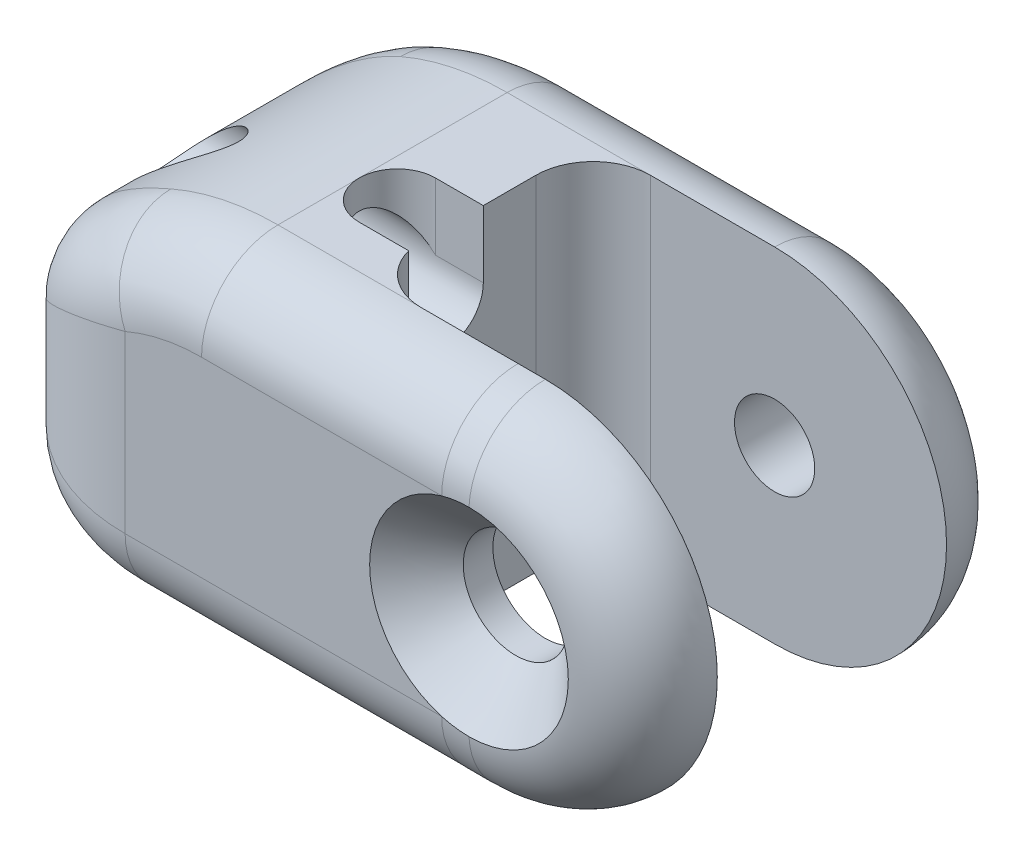
SolidWorks part; units mm, degrees
ref_plane "Front Plane" through (0, 0, 0) normal (0, 0, 1) x (1, 0, 0)
ref_plane "Top Plane" through (0, 0, 0) normal (0, 1, 0) x (1, 0, 0)
ref_plane "Right Plane" through (0, 0, 0) normal (1, 0, 0) x (0, 0, -1)
sketch "Sketch2" plane through (0, 0, 0) normal (0, 1, 0) x (1, 0, 0)
  line L0 (-3.5, 10) -> (23.5, 10)
  line L1 (23.5, 10) -> (23.5, 6)
  line L2 (23.5, 6) -> (8, 6)
  line L3 (5, 3) -> (5, -3)
  line L4 (8, -6) -> (23.5, -6)
  line L5 (23.5, -6) -> (23.5, -10)
  line L8 (-49.3622, 0) -> (56.3776, 0) construction
  line L9 (0, 21.2372) -> (0, -19.0689) construction
  line L10 (5, 3) -> (8, 3) construction
  line L11 (8, 3) -> (8, 6) construction
  line L16 (-3.5, -10) -> (23.5, -10)
  arc A0 (8, 6) -> (5, 3) centre (8, 3) ccw
  arc A1 (8, -6) -> (5, -3) centre (8, -3) cw
  arc A3 (-3.5, 10) -> (-3.5, -10) centre (-3.5, 0) ccw
  point P13 (8, 3)
  dimension "D2" = 20
  dimension "D3" = 4
  dimension "D4" = 18.5
  dimension "D5" = 12
  dimension "D6" = 3
  dimension "D7" = 3
  dimension "D8" = 5
  dimension "D9" = 27
extrude "Boss-Extrude1" add sketch "Sketch2" along normal blind 18
sketch "Sketch5" plane through (0, 0, 10) normal (0, 0, 1) x (1, 0, 0)
  line L0 (-13.5058, 9) -> (31.8434, 9) construction
  line L1 (-3.5, 18) -> (-3.5, 0) construction
  line L2 (23.5, 18) -> (23.5, 0) construction
  line L3 (-3.5, 18) -> (23.5, 18) construction
  line L4 (14.5, 18) -> (14.5, 0) construction
  line L5 (-13.5, 0) -> (-3.5, 0) construction
  line L7 (-13.5, 0) -> (-13.5, 4)
  line L8 (-13.5, 0) -> (14.5, 0)
  line L9 (0.5, 18) -> (14.5, 18)
  arc A1 (14.5, 0) -> (14.5, 18) centre (14.5, 9) ccw
  arc A2 (0.5, 18) -> (-13.5, 4) centre (0.5, 4) ccw
  dimension "D2" = 4
  dimension "D1" = 9
  dimension "D3" = 10
extrude "Cut-Extrude1" cut sketch "Sketch5" against normal blind 20 flip side to cut
sketch "Sketch6" plane through (0, 0, 10) normal (0, 0, 1) x (1, 0, 0)
  line L0 (14.5, 0) -> (14.5, 18) construction
  point P4 (14.5, 9)
hole_wizard "CSK for M5 Countersunk Flat Head Screw1" positions "Sketch7" profile "Sketch8" countersink size "M5" standard "DIN" end condition up to next
sketch "Sketch7" plane through (0, 0, 10) normal (0, 0, 1) x (1, 0, 0)
  point P0 (14.5, 9)
sketch "Sketch8" plane through (14.5, 9, 10) normal (1, 0, 0) x (0, -1, 0)
  line L0 (0, 0) -> (0, 4)
  line L1 (0, 4) -> (2.75, 4)
  line L2 (2.75, 4) -> (2.75, 2.45)
  line L3 (2.75, 2.45) -> (5.2, 0)
  line L5 (5.2, 0) -> (0, 0)
  line L6 (-2.75, 2.45) -> (-5.2, 0) construction
  line L11 (0, -6.35) -> (0, 107.95) construction
  dimension "Thru Hole Dia." = 5.5
  dimension "Thru Hole Depth" = 4
  dimension "Near C'Sink Dia." = 10.4
  dimension "Near C'Sink Angle" = 90
hole_wizard "M5 Tapped Hole1" positions "Sketch9" profile "Sketch11" tap size "M5" standard "DIN" end condition through all
sketch "Sketch9" plane through (0, 0, 10) normal (0, 0, 1) x (1, 0, 0)
  point P0 (14.5, 9)
sketch "Sketch11" plane through (14.5, 9, 10) normal (1, 0, 0) x (0, -1, 0)
  line L0 (0, 0) -> (0, 20)
  line L1 (0, 20) -> (2.1, 20)
  line L2 (2.1, 20) -> (2.1, 3.1)
  line L3 (2.1, 3.1) -> (5.2, 0)
  line L5 (5.2, 0) -> (0, 0)
  line L6 (-2.1, 3.1) -> (-5.2, 0) construction
  line L11 (0, -6.35) -> (0, 107.95) construction
  dimension "Thru Tap Drill Dia." = 4.2
  dimension "Thru Tap Drill Depth" = 20
  dimension "Near C'Sink Dia." = 10.4
  dimension "Near C'Sink Angle" = 90
cosmetic thread "Hole Thread1" parameters "D2"=5
fillet "Fillet2" radius 4 11 edges at (-9.0658, 14.2223, -8.308) (-1.5212, 17.8533, -10) (7.5, 18, -10) (23.5, 9, -10) (-9.0658, 14.2223, 8.308) (-1.5212, 17.8533, 10) (7.5, 18, 10) (23.5, 9, 10) (5.5, 0, 10) (-13.5, 0, 0) (5.5, 0, -10)
sketch "Sketch13" plane through (5, 0, 0) normal (1, 0, 0) x (0, 0, -1)
  line L0 (-1.75, -2.2721) -> (-1.75, 20.0856) construction
  line L1 (-3, 0) -> (3, 0) construction
  line L2 (-3, 18) -> (3, 18) construction
  circle A0 centre (-1.75, 14.5) radius 2
  point P4 (0, 0)
  dimension "D2" = 3.5
  dimension "D3" = 4
  dimension "D1" = 1.75
extrude "Cut-Extrude2" cut sketch "Sketch13" against normal through all both and the other way through all
sketch "Sketch14" plane through (0, 18, 0) normal (0, 1, 0) x (1, 0, 0)
  line L0 (5, 0) -> (-14.1432, 0) construction
  line L3 (5, -3) -> (5, 3) construction
  line L4 (2.5, -3.75) -> (7.4532, -3.75)
  line L5 (2.5, 0.25) -> (7.4532, 0.25)
  line L6 (7.4532, 0.25) -> (7.4532, -3.75)
  arc A0 (2.5, 0.25) -> (2.5, -3.75) centre (2.5, -1.75) ccw
  dimension "D1" = 1.75
  dimension "D2" = 2.5
extrude "Cut-Extrude3" cut sketch "Sketch14" against normal blind 3.5
